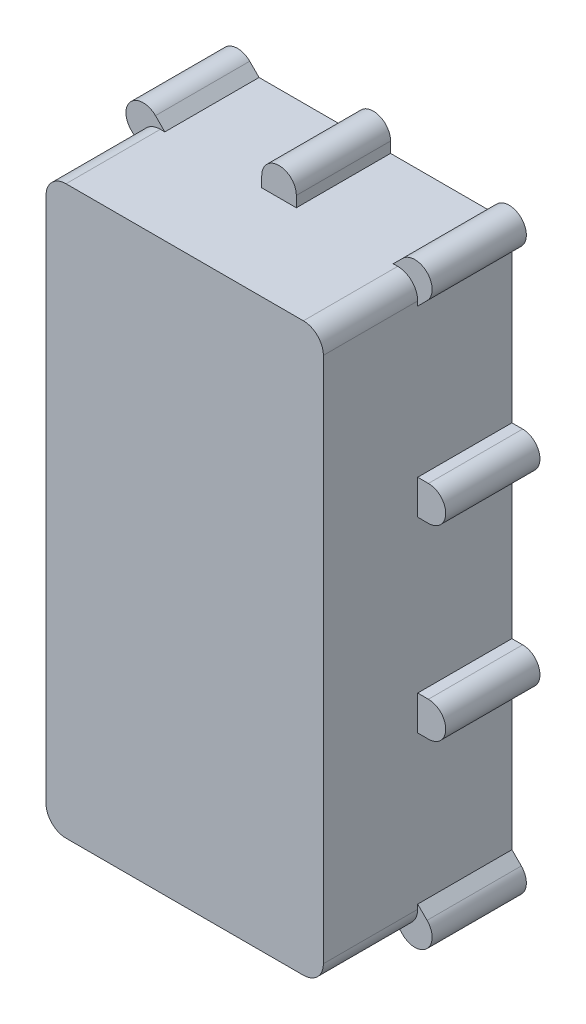
SolidWorks part; units mm, degrees
material "ABS"
ref_plane "X-Y Datum" through (0, 0, 0) normal (0, 0, 1) x (1, 0, 0)
ref_plane "X-Z Datum" through (0, 0, 0) normal (0, 1, 0) x (1, 0, 0)
ref_plane "Y-Z Datum" through (0, 0, 0) normal (1, 0, 0) x (0, 0, -1)
sketch "Sketch1" plane through (0, 0, 0) normal (0, 0, 1) x (1, 0, 0)
  line L0 (1.8162, 48.1563) -> (125.4513, 48.1563) construction
  line L1 (24.3593, 48.1563) -> (24.3593, 120.2923) construction
  line L3 (24.3593, 120.2923) -> (125.4513, 120.2923) construction
  line L8 (125.4513, 48.1563) -> (125.4513, 120.2923) construction
  line L33 (24.3593, 120.2923) -> (1.8162, 120.2923) construction
  line L34 (24.3593, 120.2923) -> (24.3593, 48.1563) construction
  line L35 (63.6337, 48.1563) -> (63.6337, 43.0763) construction
  line L36 (1.8162, 120.2923) -> (1.8162, 48.1563) construction
  line L41 (24.3593, 120.2923) -> (23.7243, 120.2923) construction
  line L42 (24.3593, 120.2923) -> (24.3593, 122.8323) construction
  line L44 (27.5343, 14.7553) -> (27.5343, 43.0763) construction
  line L45 (125.4513, 120.2923) -> (127.9913, 120.2923) construction
  line L46 (27.5343, 14.7553) -> (125.4513, 14.7553) construction
  line L47 (23.7243, 122.8323) -> (127.9913, 122.8323)
  line L48 (23.7243, 122.8323) -> (23.7243, -21.9477)
  line L49 (23.7243, -21.9477) -> (127.9913, -21.9477)
  line L50 (127.9913, 122.8323) -> (127.9913, -21.9477)
  line L51 (125.4513, 14.7553) -> (125.4513, 43.0763) construction
  line L52 (27.5343, 43.0763) -> (125.4513, 43.0763) construction
  line L53 (23.7243, 120.2923) -> (23.7243, 48.1563) construction
  circle A17 centre (30.4553, 114.1963) radius 2.1 construction
  circle A18 centre (119.8633, 115.2123) radius 2.1 construction
  circle A19 centre (119.6813, 54.2533) radius 2.1 construction
  circle A20 centre (29.4393, 53.2363) radius 2.1 construction
  circle A26 centre (31.9793, 18.4383) radius 2.1 construction
  circle A27 centre (31.9793, 39.3933) radius 2.1 construction
  circle A28 centre (120.6193, 28.8183) radius 2.1 construction
sketch "Sketch2" plane through (0, 0, 0) normal (0, 0, 1) x (1, 0, 0)
  line L4 (55.176, 122.8323) -> (127.9913, 122.8323)
  line L6 (55.176, 48.5244) -> (55.176, 50.9244) construction
  line L7 (55.176, -21.05) -> (127.9913, -21.05)
  line L8 (127.9913, 122.8323) -> (127.9913, -21.05)
  line L9 (55.176, 110.2103) -> (127.9913, -21.05) construction
  line L10 (55.176, -8.428) -> (127.9913, 122.8323) construction
  line L11 (55.176, 50.9244) -> (55.176, -21.05)
  line L12 (55.176, 50.9244) -> (55.176, 122.8323)
  circle A7 centre (88.0827, 6.45) radius 27.5
  circle A8 centre (88.0294, 95.3501) radius 27.5
  circle A9 centre (98.216, 50.8911) radius 6.477
  circle A10 centre (77.896, 50.9089) radius 6.477
  circle A11 centre (121.5143, 31.8208) radius 6.477
  circle A12 centre (115.996, 50.8756) radius 2.4
  circle A13 centre (55.176, 50.9244) radius 2.4
  point P14 (88.0827, 50.8911)
sketch "Sketch3" plane through (0, 0, 0) normal (0, 0, 1) x (1, 0, 0)
  line L7 (0, 0) -> (76.2, 0)
  line L10 (0, 0) -> (0, 168.275)
  line L11 (0, 168.275) -> (76.2, 168.275)
  line L12 (76.2, 0) -> (76.2, 168.275)
  dimension "D1" = 168.275
  dimension "D2" = 76.2
extrude "Boss-Extrude1" add sketch "Sketch3" along normal blind 53.975
shell "Shell1" thickness 6 removed face at (38.1, 84.1375, 0) outward yes
fillet "Fillet1" radius 5.334 4 edges at (76.2, 168.275, 26.9875) (76.2, 0, 26.9875) (0, 0, 26.9875) (0, 168.275, 26.9875)
fillet "Fillet2" radius 6.35 4 edges at (-6, -6, 29.9875) (-6, 174.275, 29.9875) (82.2, 174.275, 29.9875) (82.2, -6, 29.9875)
sketch "Sketch6" plane through (0, 0, 0) normal (0, 0, -1) x (-1, 0, 0)
  line L8 (-5.334, 172.5577) -> (-70.866, 172.5577)
  line L9 (-80.4827, 162.941) -> (-80.4827, 5.334)
  line L10 (-70.866, -4.2827) -> (-5.334, -4.2827)
  line L11 (4.2827, 5.334) -> (4.2827, 162.941)
  line L12 (-79.2, 162.941) -> (-79.2, 5.334)
  line L13 (-70.866, -3) -> (-5.334, -3)
  line L14 (3, 5.334) -> (3, 162.941)
  line L15 (-5.334, 171.275) -> (-70.866, 171.275)
  line L16 (-79.2, 162.941) -> (-79.2, 5.334) construction
  line L17 (-70.866, -3) -> (-5.334, -3) construction
  line L18 (3, 5.334) -> (3, 162.941) construction
  line L19 (-5.334, 171.275) -> (-70.866, 171.275) construction
  line L20 (-77.9173, 162.941) -> (-77.9173, 5.334)
  line L21 (-70.866, -1.7173) -> (-5.334, -1.7173)
  line L22 (1.7173, 5.334) -> (1.7173, 162.941)
  line L23 (-5.334, 169.9923) -> (-70.866, 169.9923)
  arc A8 (-70.866, 172.5577) -> (-80.4827, 162.941) centre (-70.866, 162.941) ccw
  arc A9 (-80.4827, 5.334) -> (-70.866, -4.2827) centre (-70.866, 5.334) ccw
  arc A10 (-5.334, -4.2827) -> (4.2827, 5.334) centre (-5.334, 5.334) ccw
  arc A11 (4.2827, 162.941) -> (-5.334, 172.5577) centre (-5.334, 162.941) ccw
  arc A12 (-70.866, 171.275) -> (-79.2, 162.941) centre (-70.866, 162.941) ccw
  arc A13 (-79.2, 5.334) -> (-70.866, -3) centre (-70.866, 5.334) ccw
  arc A14 (-5.334, -3) -> (3, 5.334) centre (-5.334, 5.334) ccw
  arc A15 (3, 162.941) -> (-5.334, 171.275) centre (-5.334, 162.941) ccw
  arc A16 (-70.866, 171.275) -> (-79.2, 162.941) centre (-70.866, 162.941) ccw construction
  arc A17 (-79.2, 5.334) -> (-70.866, -3) centre (-70.866, 5.334) ccw construction
  arc A18 (-5.334, -3) -> (3, 5.334) centre (-5.334, 5.334) ccw construction
  arc A19 (3, 162.941) -> (-5.334, 171.275) centre (-5.334, 162.941) ccw construction
  arc A20 (-77.9173, 5.334) -> (-70.866, -1.7173) centre (-70.866, 5.334) ccw
  arc A21 (-5.334, -1.7173) -> (1.7173, 5.334) centre (-5.334, 5.334) ccw
  arc A22 (1.7173, 162.941) -> (-5.334, 169.9923) centre (-5.334, 162.941) ccw
  arc A23 (-70.866, 169.9923) -> (-77.9173, 162.941) centre (-70.866, 162.941) ccw
  dimension "D4" = 7.0513
  dimension "D5" = 2.5654
  dimension "D1" = 3
  dimension "D2" = 1.2827
  dimension "D3" = 1.2827
extrude "Cut-Extrude1" cut sketch "Sketch6" against normal blind 1.2446
fillet "Fillet3" radius 0.254 16 edges at (-4.2827, 84.1375, 1.2446) (-1.466, -1.466, 1.2446) (38.1, -4.2827, 1.2446) (77.666, -1.466, 1.2446) (80.4827, 84.1375, 1.2446) (77.666, 169.741, 1.2446) (38.1, 172.5577, 1.2446) (-1.466, 169.741, 1.2446) (75.852, 167.927, 1.2446) (77.9173, 84.1375, 1.2446) (75.852, 0.348, 1.2446) (38.1, -1.7173, 1.2446) (0.348, 0.348, 1.2446) (-1.7173, 84.1375, 1.2446) (0.348, 167.927, 1.2446) (38.1, 169.9923, 1.2446)
fillet "Fillet4" radius 0.127 16 edges at (75.852, 167.927, 0) (38.1, 169.9923, 0) (0.348, 167.927, 0) (-1.7173, 84.1375, 0) (0.348, 0.348, 0) (38.1, -1.7173, 0) (75.852, 0.348, 0) (77.666, 169.741, 0) (38.1, 172.5577, 0) (-1.466, 169.741, 0) (-4.2827, 84.1375, 0) (-1.466, -1.466, 0) (38.1, -4.2827, 0) (77.666, -1.466, 0) (77.9173, 84.1375, 0) (80.4827, 84.1375, 0)
sketch "Sketch7" plane through (0, 0, 53.975) normal (0, 0, -1) x (-1, 0, 0)
  line L0 (-76.2, 32) -> (0, 32)
  line L1 (-76.2, 5.334) -> (-76.2, 162.941) construction
  line L2 (0, 162.941) -> (0, 5.334) construction
  line L3 (-76.2, 34.5) -> (0, 34.5)
  line L4 (-5.334, 0) -> (-70.866, 0) construction
  line L5 (-76.2, 32) -> (-76.2, 34.5)
  line L6 (0, 32) -> (0, 34.5)
  dimension "D2" = 32
  dimension "D1" = 2.5
extrude "Boss-Extrude2" add sketch "Sketch7" along normal up to surface (53.975 mm away) up to face at (38.1, 84.1375, 0)
sketch "Sketch8" plane through (0, 0, 0) normal (0, 0, -1) x (-1, 0, 0)
  line L0 (-5.334, 5.334) -> (5.0914, -5.0914)
  line L1 (-1.7782, -6) -> (1.2023, -8.9805)
  line L2 (-0.35, -6) -> (-75.85, -6) construction
  line L3 (-5.334, -4.2827) -> (-5.334, -4.4097)
  line L4 (4.4097, 5.334) -> (4.2827, 5.334)
  line L5 (-5.334, -4.2827) -> (-5.334, -4.4097)
  line L6 (4.4097, 5.334) -> (4.2827, 5.334)
  line L7 (6, 1.7782) -> (8.9805, -1.2023)
  line L8 (6, 167.925) -> (6, 0.35) construction
  line L9 (-38.1, -6) -> (-38.1, 174.275) construction
  line L10 (-75.85, 174.275) -> (-0.35, 174.275) construction
  line L11 (-82.2, 84.1375) -> (6, 84.1375) construction
  line L12 (-82.2, 0.35) -> (-82.2, 167.925) construction
  circle A0 centre (5.0914, -5.0914) radius 3.025
  circle A1 centre (5.0914, -5.0914) radius 5.5
  arc A3 (-5.334, -4.4097) -> (4.4097, 5.334) centre (-5.334, 5.334) ccw
  arc A4 (-5.334, -4.2827) -> (4.2827, 5.334) centre (-5.334, 5.334) ccw
  arc A5 (-5.334, -4.4097) -> (4.4097, 5.334) centre (-5.334, 5.334) ccw
  arc A6 (-5.334, -4.2827) -> (4.2827, 5.334) centre (-5.334, 5.334) ccw
  point P6 (1.5558, -1.5558)
  arc M11 (4.4097, 5.334) -> (-5.334, -4.4097) centre (-5.334, 5.334) cw
  line M14 (-75.85, -6) -> (-0.35, -6)
  arc M15 (-0.35, -6) -> (6, 0.35) centre (-0.35, 0.35) ccw
  line M16 (6, 0.35) -> (6, 167.925)
  dimension "D1" = 6.05
  dimension "D4" = 11
  dimension "D3" = 5
  dimension "D2" = 0
extrude "Boss-Extrude3" add sketch "Sketch8" against normal blind 29.972 contours A1 A0 M15 | A1 L1 M15 M14 | A1 L7 M16 M15 | A0 M15 | L0 A0 M15 | A0 L0 M15 | A1 A0 L0 M11 M15 | A1 L0 A0 M15 M11 region at (-3.9532, -1.0787, 0) region at (-1.0787, -3.9532, 0) region at (-4.2457, -2.9327, 0) region at (-2.9327, -4.2457, 0) region at (-6.789, 0.5448, 0) region at (-7.5393, -0.3393, 0) region at (0.5448, -6.789, 0) region at (-5.4552, -5.4552, 0)
sketch "Sketch9" plane through (0, 0, 0) normal (0, 0, -1) x (-1, 0, 0)
  circle A0 centre (5.0914, -5.0914) radius 3.025 construction
  circle A1 centre (5.0914, -5.0914) radius 3.025
  dimension "D1" = 6.05
extrude "Cut-Extrude2" cut sketch "Sketch9" against normal blind 9
ref_plane "Plane1" through (38.1, 0, 0) normal (-1, 0, 0) x (0, 0, 1)
ref_plane "Plane2" through (0, 84.1375, 0) normal (0, -1, 0) x (-1, 0, 0)
mirror "Mirror1" about plane through (38.1, 0, 0) normal (-1, 0, 0) of "Cut-Extrude2", "Boss-Extrude3"
mirror "Mirror2" about plane through (0, 84.1375, 0) normal (0, -1, 0) of "Cut-Extrude2", "Boss-Extrude3", "Mirror1"
sketch "Sketch10" plane through (0, 0, 0) normal (0, 0, -1) x (-1, 0, 0)
  line L0 (6, 84.1375) -> (39.3327, 84.1375) construction
  line L2 (6, 166.4968) -> (6, 1.7782) construction
  line L3 (6, 84.1375) -> (6, 157.4914)
  line L4 (6, 113.8555) -> (9.4097, 113.8555) construction
  line L5 (4.4097, 162.941) -> (4.4097, 5.334) construction
  line L7 (9.4097, 119.3555) -> (6, 119.3555)
  line L9 (9.4097, 108.3555) -> (6, 108.3555)
  line L10 (9.4097, 48.9195) -> (6, 48.9195)
  line L11 (9.4097, 59.9195) -> (6, 59.9195)
  circle A4 centre (9.4097, 113.8555) radius 3.025
  circle A5 centre (9.4097, 113.8555) radius 5.5
  circle A6 centre (9.4097, 54.4195) radius 3.025
  circle A7 centre (9.4097, 54.4195) radius 5.5
  point P0 (5.0914, 173.3664)
  point P1 (5.0914, -5.0914)
  point P3 (-81.2914, -5.0914)
  line M14 (6, 1.7782) -> (6, 166.4968)
  line M21 (4.4097, 162.941) -> (4.4097, 5.334)
  dimension "D3" = 89.2289
  dimension "D4" = 6.05
  dimension "D5" = 11
  dimension "D1" = 178.4577
  dimension "D2" = 86.3827
  dimension "D6" = 5
  dimension "D7" = 29.718
  dimension "D8" = 59.5109
  dimension "D9" = 59.436
  dimension "D10" = 59.5109
extrude "Boss-Extrude4" add sketch "Sketch10" against normal blind 29.972 contours A7 A6 M14 | A7 L11 M14 | A7 M14 M21 | L10 A7 M14 | A6 | A5 L7 L3 | A5 L3 L9 | A5 A4 M14 | A5 M14 M21 | A4 region at (-6.833, 108.7032, 0) region at (-6.833, 59.5718, 0) region at (-5.2799, 113.8555, 0) region at (-6.1416, 113.8555, 0) region at (-13.1987, 58.2085, 0) region at (-5.2799, 54.4195, 0) region at (-6.833, 119.0078, 0) region at (-6.833, 49.2672, 0) region at (-9.4097, 113.8555, 0) region at (-9.4097, 54.4195, 0)
sketch "Sketch11" plane through (0, 0, 0) normal (0, 0, -1) x (-1, 0, 0)
  circle A0 centre (9.4097, 54.4195) radius 3.025 construction
  circle A1 centre (9.4097, 113.8555) radius 3.025 construction
  circle A2 centre (9.4097, 54.4195) radius 3.025
  circle A3 centre (9.4097, 113.8555) radius 3.025
  dimension "D1" = 6.05
extrude "Cut-Extrude3" cut sketch "Sketch11" against normal blind 9
mirror "Mirror3" about plane through (38.1, 0, 0) normal (-1, 0, 0) of "Cut-Extrude3", "Boss-Extrude4"
sketch "Sketch12" plane through (0, 0, 0) normal (0, 0, -1) x (-1, 0, 0)
  line L0 (-74.4218, -6) -> (-1.7782, -6)
  line L1 (-38.1, -6) -> (-38.1, -9.4097) construction
  line L2 (-5.334, -4.4097) -> (-70.866, -4.4097) construction
  line L3 (-43.6, -9.4097) -> (-43.6, -6)
  line L4 (-32.6, -9.4097) -> (-32.6, -6)
  circle A0 centre (-38.1, -9.4097) radius 3.025
  circle A1 centre (-38.1, -9.4097) radius 5.5
  point P15 (-81.2914, -5.0914)
  point P16 (5.0914, -5.0914)
  line M16 (-74.4218, -6) -> (-1.7782, -6)
  line M42 (-5.334, -4.4097) -> (-70.866, -4.4097)
  dimension "D2" = 6.05
  dimension "D4" = 11
  dimension "D1" = 43.1914
  dimension "D3" = 5
  dimension "D5" = 86.3827
extrude "Boss-Extrude5" add sketch "Sketch12" against normal blind 29.972 contours A1 L0 A0 M16 | A1 L0 L3 | A1 L4 L0 | A0 | L0 A1 M16 M42 region at (43.2523, -6.833, 0) region at (38.1, -5.2799, 0) region at (38.1, -6.1416, 0) region at (32.9477, -6.833, 0) region at (38.1, -9.4097, 0)
sketch "Sketch13" plane through (0, 0, 0) normal (0, 0, -1) x (-1, 0, 0)
  circle A0 centre (-38.1, -9.4097) radius 3.025 construction
  circle A1 centre (-38.1, -9.4097) radius 3.025
extrude "Cut-Extrude4" cut sketch "Sketch13" against normal blind 9
mirror "Mirror4" about plane through (0, 84.1375, 0) normal (0, -1, 0) of "Cut-Extrude4", "Boss-Extrude5"
sketch "Sketch17" plane through (-6, 0, 0) normal (-1, 0, 0) x (0, 0, 1)
  line L0 (59.975, 167.925) -> (59.975, 0.35) construction
  line L1 (0, 34.5) -> (53.975, 34.5) construction
  line L2 (53.975, 32) -> (53.975, 5.334) construction
  circle A0 centre (38.385, 85.3) radius 9.525
  circle A1 centre (38.385, 85.3) radius 14.2875
  circle A2 centre (38.385, 18.667) radius 6.35
  circle A3 centre (38.385, 18.667) radius 10.795
  point P10 (53.975, 18.667)
  dimension "D1" = 19.05
  dimension "D4" = 28.575
  dimension "D5" = 12.7
  dimension "D6" = 21.59
  dimension "D2" = 21.59
  dimension "D3" = 50.8
extrude "Cut-Extrude6" cut sketch "Sketch17" against normal blind 6 contours A0 | A2 region at (-6, 85.3, 38.385) region at (-6, 18.667, 38.385)
sketch "Sketch18" plane through (0, 0, 0) normal (1, 0, 0) x (0, 0, -1)
  circle A0 centre (-38.385, 85.3) radius 14.2875 construction
  circle A1 centre (-38.385, 85.3) radius 14.2875
  circle A2 centre (-38.385, 18.667) radius 10.795 construction
  circle A3 centre (-38.385, 18.667) radius 10.795
extrude "Cut-Extrude7" cut sketch "Sketch18" against normal blind 3
